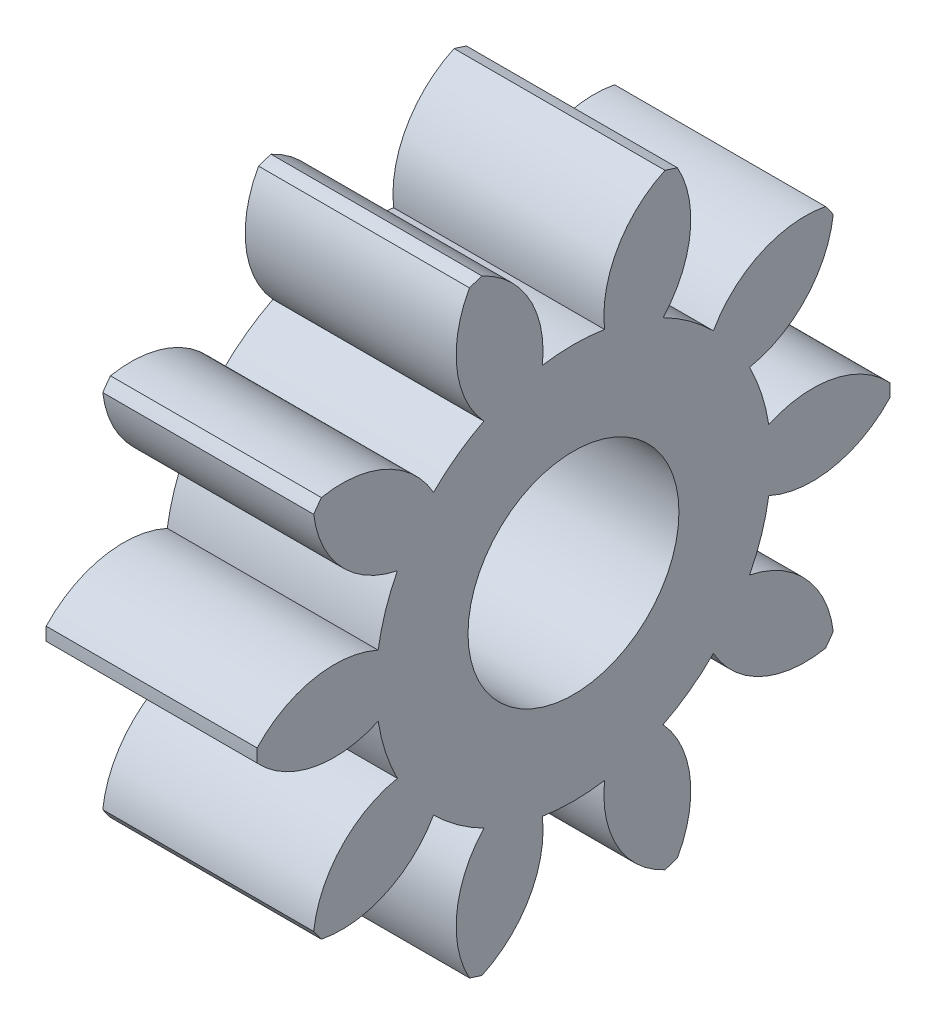
SolidWorks part; units mm, degrees
ref_plane "Plane1" through (0, 0, 0) normal (0, 0, 1) x (1, 0, 0)
ref_plane "Plane2" through (0, 0, 0) normal (0, 1, 0) x (1, 0, 0)
ref_plane "Plane3" through (0, 0, 0) normal (1, 0, 0) x (0, 0, -1)
sketch "HoldingSke" plane through (0, 0, 0) normal (0, 1, 0) x (1, 0, 0)
  line L0 (0, 0) -> (0.6565, -0.1158)
  line L1 (-15, 0) -> (100, 0) construction
  line L2 (0, 0) -> (-2.1039, 2.3779)
  line L3 (0, 0) -> (-11.863, 4.5341)
  line L4 (0, 0) -> (8.5048, 1.4996)
  line L5 (0, 0) -> (-46.8476, -17.4728)
  line L6 (0, 0) -> (-4.9738, -3.3558)
  line L7 (-2.1039, 2.3779) -> (8.6586, 51.2059)
  line L8 (-76.2, 54.61) -> (-75.2, 54.61)
  line L9 (-71.009, 38.7566) -> (-53.1078, 45.2721)
  line L10 (-76.2, 71.12) -> (104.1128, 71.12)
  line L11 (0, 0) -> (-6, 0)
  line L12 (-76.2, 101.6) -> (-76.147, 101.6)
  line L13 (24.9733, 27.94) -> (52.9518, 28.4284)
  line L14 (24.9733, 27.94) -> (24.9743, 27.94)
  line L15 (24.9733, 27.94) -> (100.4006, 29.5858)
  line L16 (-63.627, -1.5) -> (-12.827, -1.5)
  circle A0 centre (0, 0) radius 3
  circle A1 centre (0, 0) radius 5.624
  circle A2 centre (0, 0) radius 37.5
  circle A3 centre (0, 0) radius 3
  dimension "Num_teeth" = 10
  dimension "Pitch_radius" = 180.3128
  dimension "Width" = 6
  dimension "Thickness" = 6
sketch "BasProSke" plane through (0, 0, 0) normal (0, 1, 0) x (1, 0, 0)
  line L0 (-10, 0) -> (60, 0) construction
  line L1 (0, 0) -> (0, 9)
  line L2 (0, 0) -> (6, 0)
  line L3 (6, 0) -> (6, 9)
  line L4 (6, 9) -> (0, 9)
  dimension "Thickness" = 6
  dimension "Diameter" = 18
revolve "Base-Revolve" add sketch "BasProSke" angle 360 about L0
sketch "TooCutSke" plane through (0, 0, 0) normal (1, 0, 0) x (0, 0, -1)
  line L1 (0, 0) -> (0, 107) construction
  line L2 (0, 0) -> (-1.2658, 7.3924) construction
  line L3 (0, 0) -> (-4.5869, 14.117) construction
  line L4 (-1.2658, 7.3924) -> (-2.2934, 7.0585) construction
  arc A0 (0.8839, 5.5541) -> (-0.8839, 5.5541) centre (0, 0) ccw
  arc A1 (2.6378, 8.6313) -> (-2.6378, 8.6313) centre (0, 0) ccw
  circle A2 centre (0, 0) radius 7.5 construction
  circle A3 centre (0, 0) radius 7.0477 construction
  arc A4 (-0.8839, 5.5541) -> (-2.6378, 8.6313) centre (-3.8646, 5.8936) ccw
  arc A5 (2.6378, 8.6313) -> (0.8839, 5.5541) centre (3.8646, 5.8936) ccw
extrude "ToothCut" cut sketch "TooCutSke" along normal through all
fillet "Breaks" [suppressed] radius 0.03 tangent propagation no
fillet "RootFillets" [suppressed] radius 0.376
pattern_circular "TeethCuts" count 10 over 360 about axis through (-10, 0, 0) along (1, 0, 0) of "ToothCut", "RootFillets", "Breaks"
sketch "HubNeaOneSke" plane through (0, 0, 0) normal (-1, 0, 0) x (0, 0, 1)
  circle A0 centre (0, 0) radius 5.624
  dimension "Diameter" = 11.248
extrude "HubNearOne" [suppressed] add sketch "HubNeaOneSke" along normal blind 44.0001
sketch "HubNeaBotSke" plane through (0, 0, 0) normal (-1, 0, 0) x (0, 0, 1)
  circle A0 centre (0, 0) radius 5.624
  dimension "Diameter" = 11.248
extrude "HubNearBoth" [suppressed] add sketch "HubNeaBotSke" along normal blind 22
ref_plane "FarPln" through (6, 0, 0) normal (1, 0, 0) x (0, 0, -1)
sketch "HubFarSke" plane through (6, 0, 0) normal (1, 0, 0) x (0, 0, -1)
  circle A0 centre (0, 0) radius 5.624
  dimension "Diameter" = 11.248
extrude "HubFar" [suppressed] add sketch "HubFarSke" along normal blind 22
sketch "BorSke" plane through (0, 0, 0) normal (1, 0, 0) x (0, 0, -1)
  circle A0 centre (0, 0) radius 3
  dimension "Diameter" = 6
extrude "Bore" cut sketch "BorSke" along normal mid plane 100.0001
sketch "KeySke" plane through (0, 0, 0) normal (1, 0, 0) x (0, 0, -1)
  line L0 (-1, 0) -> (-1, 4)
  line L1 (-1, 4) -> (1, 4)
  line L2 (1, 4) -> (1, 0)
  line L3 (0, 0) -> (0, 34) construction
  line L4 (-1, 0) -> (1, 0)
  dimension "Width" = 2
extrude "Keyway" [suppressed] cut sketch "KeySke" along normal mid plane 100.0001
pattern_circular "Keyway2" [suppressed] count 2 every 90 about axis through (-10, 0, 0) along (1, 0, 0) reverse direction yes
equation "' \"Module@HoldingSke\" = 6.35"
equation "' \"Num_teeth@HoldingSke\" = 12"
equation "' \"Ap@HoldingSke\" =  20"
equation "' \"Ap@HoldingSke\" = 20"
equation "' \"Width@HoldingSke\" = 0.5 * 25.4"
equation "' \"Hub_dia@HoldingSke\"= 1 * 25.4"
equation "' \"Hub_dia@HoldingSke\" = 1 * 25.4"
equation "' \"Overall_len@HoldingSke\" = 1.0 * 25.4"
equation "' \"Bore@HoldingSke\" = 0.75 * 25.4"
equation "' \"T_dim@HoldingSke\" = 0.1 * 25.4"
equation "' \"Width@KeySke\" = 0.25 * 25.4"
equation "' \"Show_teeth@HoldingSke\" = 13"
equation "' \"Backlash@HoldingSke\" = 0.009 * 25.4"
equation "' \"Addendum_fac@HoldingSke\" = 1.0"
equation "' \"Dedendum_fac@HoldingSke\" = 1.25"
equation "' \"Dedendum_add@HoldingSke\" = 0.00005 * 25.4"
equation "' \"Clearance_fac@HoldingSke\" = 0.25"
equation "\"Pitch@HoldingSke\" = 1 / \"Module@HoldingSke\""
equation "\"Overcut_dia@TooCutSke\" = (\"Num_teeth@HoldingSke\" + 2 * \"Addendum_fac@HoldingSke\") / \"Pitch@HoldingSke\" + 0.002 * 25.4"
equation "\"Pitch_dia@TooCutSke\" = \"Num_teeth@HoldingSke\" / \"Pitch@HoldingSke\""
equation "\"Base_dia@TooCutSke\" = \"Num_teeth@HoldingSke\" / \"Pitch@HoldingSke\" * cos((\"Ap@HoldingSke\"  * 3.14159265 / 180))"
equation "\"Root_dia@TooCutSke\" = (\"Num_teeth@HoldingSke\" + 2) / \"Pitch@HoldingSke\" - 2 * (\"Addendum_fac@HoldingSke\" + \"Dedendum_fac@HoldingSke\") / \"Pitch@HoldingSke\" - \"Dedendum_add@HoldingSke\" * 2"
equation "\"Half_ang@TooCutSke\" = 180 / \"Num_teeth@HoldingSke\""
equation "\"Half_CT@TooCutSke\" = \"Num_teeth@HoldingSke\" / \"Pitch@HoldingSke\" * sin((3.14159265 / 2 / \"Num_teeth@HoldingSke\")) / 2 - 7 * \"Backlash@HoldingSke\" / 4"
equation "\"Flank_rad@TooCutSke\" = \"Num_teeth@HoldingSke\" / \"Pitch@HoldingSke\" / 5"
equation "\"Radius@RootFillets\" = \"Clearance_fac@HoldingSke\" / \"Pitch@HoldingSke\" + \"Dedendum_add@HoldingSke\""
equation "\"Break_rad@Breaks\" = 0.02 / \"Pitch@HoldingSke\""
equation "\"Thickness@HoldingSke\" = \"Width@HoldingSke\""
equation "\"OAL@HoldingSke\" = \"Thickness@HoldingSke\""
equation "\"MHD@HoldingSke\" = (\"Num_teeth@HoldingSke\" + 2) / \"Pitch@HoldingSke\" - 2 * (\"Addendum_fac@HoldingSke\" + \"Dedendum_fac@HoldingSke\")  / \"Pitch@HoldingSke\" - \"Dedendum_add@HoldingSke\" * 2"
equation "\"MBD@HoldingSke\" = (\"Num_teeth@HoldingSke\" + 2) / \"Pitch@HoldingSke\" - 2 * (\"Addendum_fac@HoldingSke\" + \"Dedendum_fac@HoldingSke\")  / \"Pitch@HoldingSke\" - \"Dedendum_add@HoldingSke\" * 2 - 0.002 * 25.4"
equation "\"MHD@HoldingSke\" = ((sgn( \"MHD@HoldingSke\" - \"Hub_dia@HoldingSke\" )-1)*( \"MHD@HoldingSke\" - \"Hub_dia@HoldingSke\" ))/-2+ \"Hub_dia@HoldingSke\""
equation "\"MBD@HoldingSke\" = ((sgn( \"MBD@HoldingSke\" - \"Bore@HoldingSke\" )-1)*( \"MBD@HoldingSke\" - \"Bore@HoldingSke\" ))/-2+ \"Bore@HoldingSke\""
equation "\"OAL@HoldingSke\" = ((sgn( \"OAL@HoldingSke\" - \"Overall_len@HoldingSke\" )+1)*( \"OAL@HoldingSke\" - \"Overall_len@HoldingSke\" ))/2 + \"Overall_len@HoldingSke\" + 0.000002 * 25.4"
equation "\"Num_teeth@TeethCuts\" = int( \"Show_teeth@HoldingSke\" ) + 1"
equation "\"Num_teeth@TeethCuts\" = ((sgn( \"Num_teeth@TeethCuts\" - \"Num_teeth@HoldingSke\" )-1)*( \"Num_teeth@TeethCuts\" - \"Num_teeth@HoldingSke\" ))/-2+ \"Num_teeth@HoldingSke\""
equation "\"Num_teeth@TeethCuts\" = ((sgn( \"Num_teeth@TeethCuts\" - 2.0)+1)*( \"Num_teeth@TeethCuts\" - 2.0))/2 +2.0"
equation "\"Angle@TeethCuts\" = 360.0 / \"Num_teeth@HoldingSke\""
equation "\"Diameter@BasProSke\" = (\"Num_teeth@HoldingSke\" + 2 * \"Addendum_fac@HoldingSke\") / \"Pitch@HoldingSke\""
equation "\"Thickness@BasProSke\"  = \"Thickness@HoldingSke\""
equation "' \"Fillet_rad@BasProSke\" =  \"Thickness@HoldingSke\" * 0.05"
equation "' \"Fillet_rad@BasProSke\" = \"Thickness@HoldingSke\" * 0.05"
equation "\"MHD@HoldingSke\" = ((sgn( \"MHD@HoldingSke\" - \"Root_dia@TooCutSke\" )-1)*( \"MHD@HoldingSke\" - \"Root_dia@TooCutSke\" ))/-2+ \"Root_dia@TooCutSke\""
equation "\"Diameter@HubNeaOneSke\" = \"MHD@HoldingSke\""
equation "\"Length@HubNearOne\" = \"OAL@HoldingSke\" - \"Thickness@BasProSke\""
equation "\"Diameter@HubNeaBotSke\" = \"MHD@HoldingSke\""
equation "\"Length@HubNearBoth\" = ( \"OAL@HoldingSke\" - \"Thickness@BasProSke\" ) / 2.0"
equation "\"Thickness@FarPln\" = \"Thickness@BasProSke\""
equation "\"Diameter@HubFarSke\" = \"MHD@HoldingSke\""
equation "\"Length@HubFar\" = ( \"OAL@HoldingSke\" - \"Thickness@BasProSke\" ) / 2.0"
equation "\"Diameter@BorSke\" = \"MBD@HoldingSke\""
equation "\"D1@Bore\" = \"OAL@HoldingSke\" * 2.0"
equation "\"D1@Keyway\" = \"OAL@HoldingSke\" * 2.0"
equation "\"Offset@KeySke\" = \"T_dim@HoldingSke\" + \"MBD@HoldingSke\" / 2.0"
